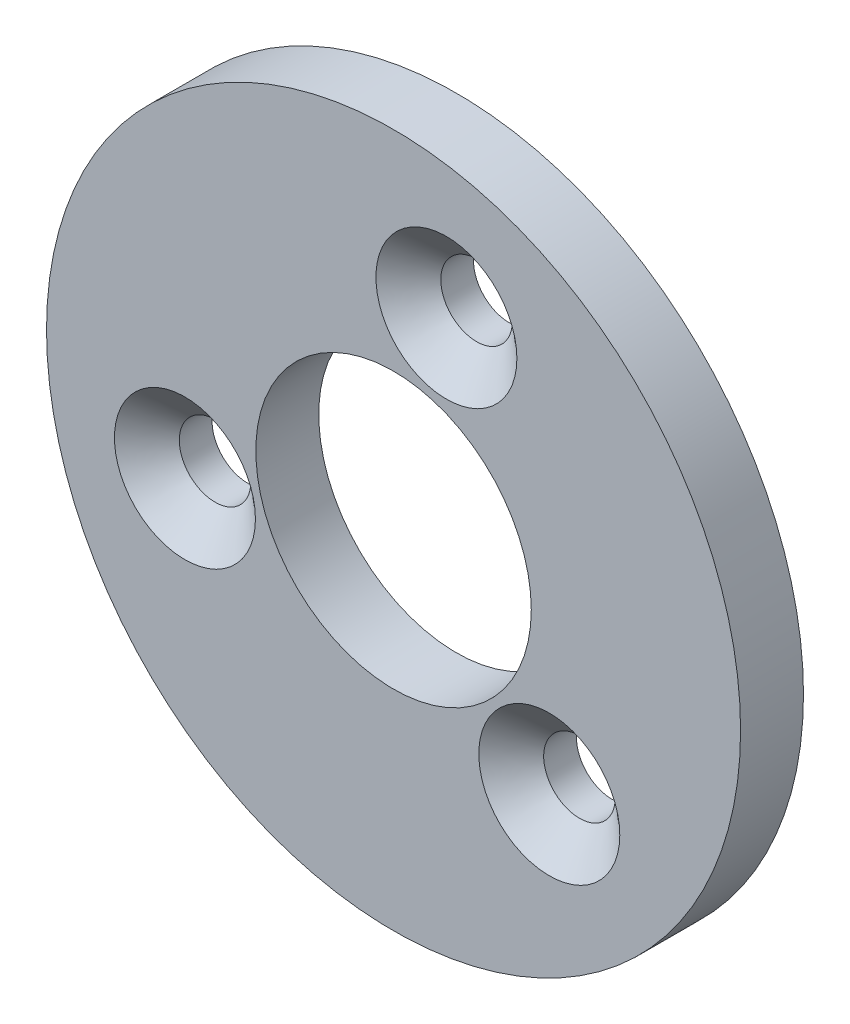
SolidWorks part; units mm, degrees
ref_plane "Front Plane" through (0, 0, 0) normal (0, 0, 1) x (1, 0, 0)
ref_plane "Top Plane" through (0, 0, 0) normal (0, 1, 0) x (1, 0, 0)
ref_plane "Right Plane" through (0, 0, 0) normal (1, 0, 0) x (0, 0, -1)
sketch "Sketch1" plane through (0, 0, 0) normal (0, 0, 1) x (1, 0, 0)
  circle A0 centre (0, 0) radius 16
  dimension "D1" = 32
extrude "Boss-Extrude1" add sketch "Sketch1" along normal blind 2.9
sketch "Sketch2" plane through (0, 0, 2.9) normal (0, 0, 1) x (1, 0, 0)
  circle A3 centre (-9.6176, -2.7388) radius 1.65
  circle A4 centre (-9.6176, -2.7388) radius 1.65
  circle A5 centre (7.1807, -6.9597) radius 1.65
  circle A6 centre (7.1807, -6.9597) radius 1.65
  circle A7 centre (2.437, 9.6985) radius 1.65
  circle A8 centre (2.437, 9.6985) radius 1.65
  dimension "D2" = 0
  dimension "D3" = 0
  dimension "D4" = 0
extrude "Cut-Extrude1" cut sketch "Sketch2" against normal through all
chamfer "Chamfer1" distance 1.6 angle 41 3 edges at (-7.9676, -2.7388, 2.9) (4.087, 9.6985, 2.9) (8.8307, -6.9597, 2.9) first distance on face at (8.8307, -6.9597, 2.9)
sketch "Sketch3" plane through (0, 0, 2.9) normal (0, 0, 1) x (1, 0, 0)
  circle A1 centre (0, 0) radius 6.35
  circle A2 centre (0, 0) radius 6.35
  dimension "D1" = 0
extrude "Cut-Extrude2" cut sketch "Sketch3" against normal through all
equation "\"smallPulleyTeeth\"= 15"
equation "\"largePulleyTeeth\"= 40"
equation "\"eighthThick\"= 2.9mm"
equation "\"sixteenthThick\" = 1.7mm"
equation "\"quarterThick\"=5.9mm"
equation "\"OD\" = 145mm"
equation "\"puckAngle\" = 60.5deg"
equation "\"puckDiam\" = 76.5mm"
equation "\"axlePress\" = 5.9mm"
equation "\"press\" = 0.2mm"
equation "\"wheelClear\" = 0.3mm"
equation "\"10-32clear\" = 4.5mm"
equation "\"D1@Boss-Extrude1\"=\"eighthThick\""
equation "\"D1@Chamfer1\"=(6.5-\"6-32clear\")/2"
equation "\"6-32clear\" = 3.3mm"
equation "\"8-32clear\" = 4.0mm"
